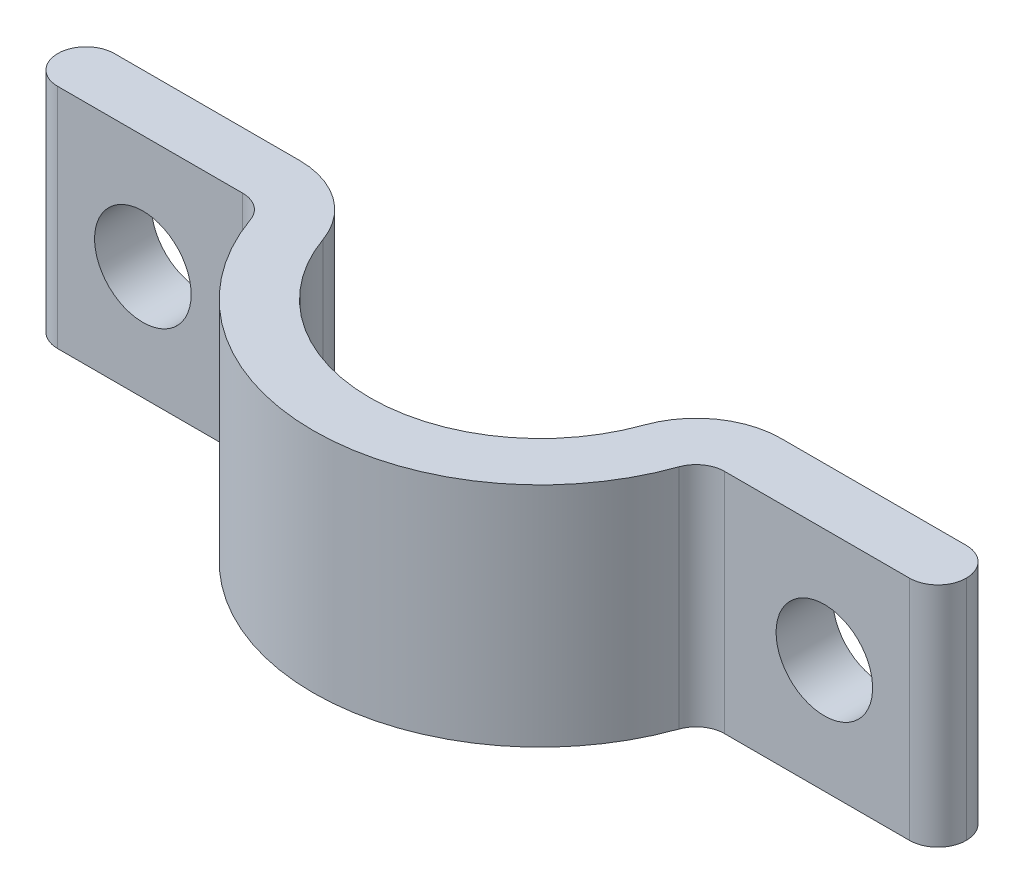
SolidWorks part; units mm, degrees
ref_plane "Front Plane" through (0, 0, 0) normal (0, 0, 1) x (1, 0, 0)
ref_plane "Top Plane" through (0, 0, 0) normal (0, 1, 0) x (1, 0, 0)
ref_plane "Right Plane" through (0, 0, 0) normal (1, 0, 0) x (0, 0, -1)
sketch "Sketch1" plane through (0, 0, 0) normal (0, 1, 0) x (1, 0, 0)
  line L0 (-16, 0) -> (-8.4853, 0)
  line L1 (-16, 0) -> (-16, -2)
  line L2 (-16, -2) -> (-8.4853, -2)
  line L3 (0, -6) -> (0, -8)
  line L4 (0, -55) -> (0, 55) construction
  line L5 (0, -8) -> (-7.5415, -8) construction
  line L8 (-55, 0) -> (55, 0) construction
  arc A0 (-8.4853, 0) -> (-5.6569, -2) centre (-8.4853, -3) cw
  arc A1 (-5.6569, -2) -> (0, -6) centre (0, 0) ccw
  arc A2 (-8.4853, -2) -> (-7.5425, -2.6667) centre (-8.4853, -3) cw
  arc A3 (-7.5425, -2.6667) -> (0, -8) centre (0, 0) ccw
  arc A4 (-7.5425, -2.6667) -> (-8, 0) centre (0, 0) cw construction
  dimension "D4" = 1
  dimension "D1" = 2
  dimension "D2" = 16
  dimension "D3" = 8
extrude "Boss-Extrude1" add sketch "Sketch1" along normal blind 8
sketch "Sketch2" plane through (0, 0, 2) normal (0, 0, 1) x (1, 0, 0)
  line L0 (-12, 8) -> (-12, 0) construction
  line L1 (-16, 8) -> (-8.4853, 8) construction
  line L2 (-16, 0) -> (-8.4853, 0) construction
  line L3 (-16, 4) -> (-8, 4) construction
  line L4 (-16, 8) -> (-16, 0) construction
  circle A0 centre (-12, 4) radius 1.7
  dimension "D1" = 3.4
extrude "Cut-Extrude1" cut sketch "Sketch2" against normal through all
fillet "Fillet1" radius 1 2 edges at (-16, 4, 0) (-16, 4, 2)
mirror "Mirror1" about plane through (0, 8, 6) normal (-1, 0, 0) of bodies 103 101
equation "\"M3_d\"= 3.4"
equation "\"D1@Sketch2\"=\"M3_d\""
